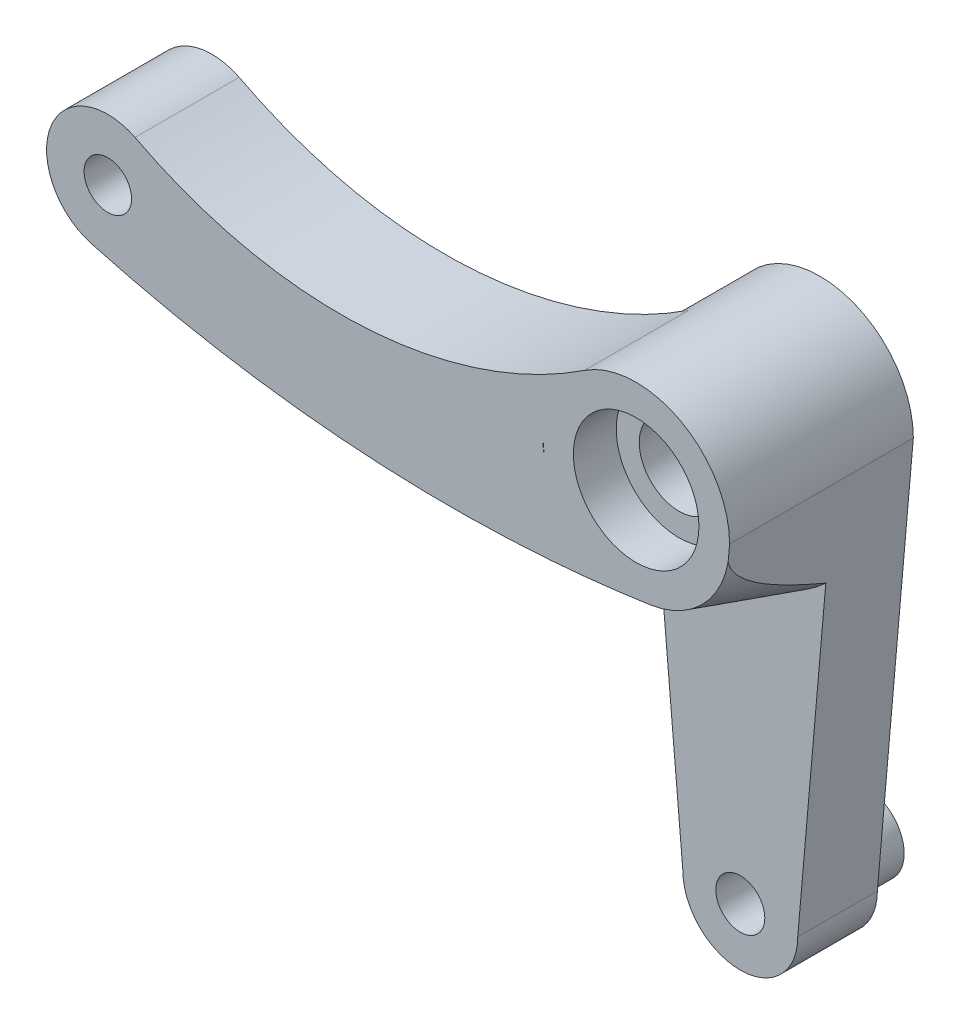
SolidWorks part; units mm, degrees
ref_plane "前视基准面" through (0, 0, 0) normal (0, 0, 1) x (1, 0, 0)
ref_plane "上视基准面" through (0, 0, 0) normal (0, 1, 0) x (1, 0, 0)
ref_plane "右视基准面" through (0, 0, 0) normal (1, 0, 0) x (0, 0, -1)
sketch "草图1" plane through (0, 0, 0) normal (0, 0, 1) x (1, 0, 0)
  line L0 (-3.75, -26.8) -> (-6.1, 0)
  line L1 (6.1, 0) -> (3.75, -26.8)
  arc A0 (6.1, 0) -> (-6.1, 0) centre (0, 0) ccw
  arc A1 (-3.75, -26.8) -> (3.75, -26.8) centre (0, -26.8) ccw
  circle A2 centre (0, 0) radius 2.6
  circle A3 centre (0, -26.8) radius 1.6
extrude "凸台-拉伸1" add sketch "草图1" along normal blind 12
sketch "草图3" plane through (0, 0, 12) normal (0, 0, 1) x (1, 0, 0)
  line L0 (-6.0069, -1.0616) -> (-3.75, -26.8)
  line L1 (3.75, -26.8) -> (6.0069, -1.0616)
  arc A0 (-6.0069, -1.0616) -> (6.0069, -1.0616) centre (0, 0) ccw
  arc A1 (-3.75, -26.8) -> (3.75, -26.8) centre (0, -26.8) ccw
extrude "切除-拉伸1" cut sketch "草图3" against normal blind 6.8
sketch "草图4" plane through (0, 0, 0) normal (0, 0, -1) x (-1, 0, 0)
  circle A0 centre (0, 0) radius 4.1
  dimension "D1" = 8.2
extrude "切除-拉伸2" cut sketch "草图4" against normal blind 2.8
sketch "草图5" plane through (0, 0, 0) normal (0, 0, -1) x (-1, 0, 0)
  circle A0 centre (0, -26.8) radius 2.5
  circle A1 centre (0, -26.8) radius 1.6
  dimension "D1" = 5
extrude "凸台-拉伸2" add sketch "草图5" along normal blind 3
chamfer "倒角1" distance 0.5 distance2 0.5 1 edges at (2.5, -26.8, 0)
sketch "草图6" plane through (0, 0, 12) normal (0, 0, 1) x (1, 0, 0)
  circle A0 centre (0, 0) radius 2.6
  circle A1 centre (0, 0) radius 4.1
  dimension "D1" = 8.2
extrude "切除-拉伸3" cut sketch "草图6" against normal blind 2.8
sketch "草图7" plane through (0, 0, 5.2) normal (0, 0, 1) x (1, 0, 0)
  line L0 (3.5514, 0) -> (-30.4486, 0) construction
  line L1 (-32.95, 0) -> (-34.5, 0) construction
  circle A0 centre (-34.5, 0) radius 1.55
  arc A1 (-3.365, 5.0879) -> (0.9013, -6.0331) centre (0, 0) ccw
  arc A2 (-32.7223, 3.5833) -> (-35.5572, -3.8578) centre (-34.5, 0) ccw
  arc A3 (-35.5572, -3.8578) -> (0.9013, -6.0331) centre (-12.1717, 81.4759) ccw
  arc A4 (-32.7223, 3.5833) -> (-3.365, 5.0879) centre (-19.3185, 29.2095) ccw
extrude "凸台-拉伸3" add sketch "草图7" along normal blind 6.8
chamfer "倒角2" distance 6.8 distance2 2 2 edges at (-2.2967, -6.4514, 5.2) (4.2555, -4.3704, 5.2) first distance on face at (-15.0102, -5.9571, 7.92) first distance on face at (3.8548, -3.9589, 8.6)
